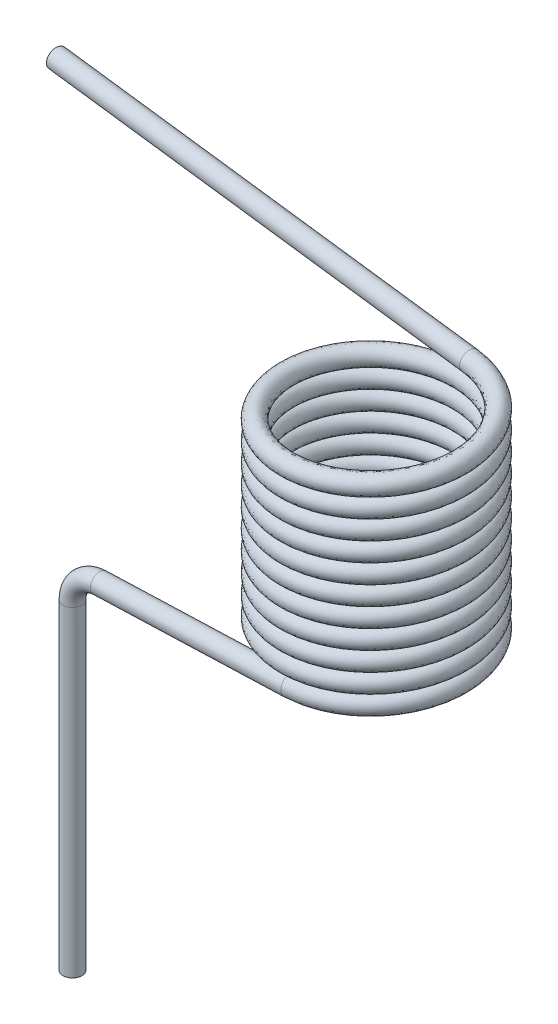
SolidWorks part; units mm, degrees
note: '?' marks a value the reader was unsure of.
ref_plane "Front" through (0, 0, 0) normal (0, 0, 1) x (1, 0, 0)
ref_plane "Top" through (0, 0, 0) normal (0, 1, 0) x (1, 0, 0)
ref_plane "Right" through (0, 0, 0) normal (1, 0, 0) x (0, 0, -1)
ref_axis "Axis1" through (0, -0.4929, 0) along (0, 1, 0)?
sketch "Sketch1" plane through (0, 0, 0) normal (0, 1, 0) x (1, 0, 0)
  circle A0 centre (0, 0) radius 1.1557
  dimension "Dm" = 2.3114
curve "Helix" pitch 0.2543 height 2.667 turns 10.4861 parameters "Body Height"=2.667, "L"=0.2543
ref_plane "Plane1" through (0, 0, 1.1557) normal (0, 0, 1) x (1, 0, 0)
ref_plane "Plane5" through (0.1007, 2.667, -1.1513) normal (-0.9956, 0.035, -0.0871) x (-0.0714, 0.3203, 0.9446)
ref_plane "Plane6" through (0, 2.667, 0) normal (0, 1, 0) x (-1, 0, 0)
ref_axis "Axis2" through (0.008, 2.667, -0.0909) along (0.0872, 0, -0.9962)?
ref_plane "Plane8" through (0.1007, 2.667, -1.1513) normal (0.0872, 0, -0.9962) x (-0.9962, 0, -0.0872)
sketch "Sketch2" plane through (0, 0, 1.1557) normal (0, 0, 1) x (1, 0, 0)
  line L0 (0, 0) -> (2.5534, -0.0894) construction
  line L1 (0, 0) -> (-2.54, 0) construction
  line L2 (0, 0) -> (5.2602, 0) construction
  line L3 (0, 0) -> (2.5534, 0.0894) construction
  line L4 (0, 0) -> (-2.5533, -0.0894)
  line L5 (-2.921, -0.4702) -> (-2.921, -4.7752)
  arc A0 (-2.5533, -0.0894) -> (-2.921, -0.4702) centre (-2.54, -0.4702) ccw
  dimension "D2" = 0.381
  dimension "D1" = 2.006
  dimension "D3" = 4.7752
  dimension "D4" = 2.921
sketch "Sketch4" plane through (0.1007, 2.667, -1.1513) normal (0.0872, 0, -0.9962) x (-0.9962, 0, -0.0872)
  line L0 (0, 0) -> (6.096, -0.2135) construction
  line L1 (0, 0) -> (4.1234, 0) construction
  line L2 (0, 0) -> (6.096, 0.2135)
  line L3 (0, -3.1599) -> (0, 1.0392) construction
  dimension "D1" = 2.006
  dimension "D2" = 2.667
  dimension "D3" = 6.096
ref_plane "Plane4" through (-5.9721, 2.8805, -1.6826) normal (-0.9956, 0.035, -0.0871) x (-0.0655, 0.405, 0.9119)
sketch "Sketch5" plane through (-5.9721, 2.8805, -1.6826) normal (-0.9956, 0.035, -0.0871) x (-0.0655, 0.405, 0.9119)
  circle A0 centre (0, 0) radius 0.127
  dimension "D1" = 0.254
curve "CompCurve2"
sweep "Sweep4" add profiles "Sketch5" path "CompCurve2"
equation "\"D1@Sketch2\" =  atn( \"L@Helix\"/( pi  * \"Dm@Sketch1\") ) "
equation "\"D2@Sketch4\" = \"Body Height@Helix\""
equation "\"D1@Sketch4\" = \"D1@Sketch2\""
